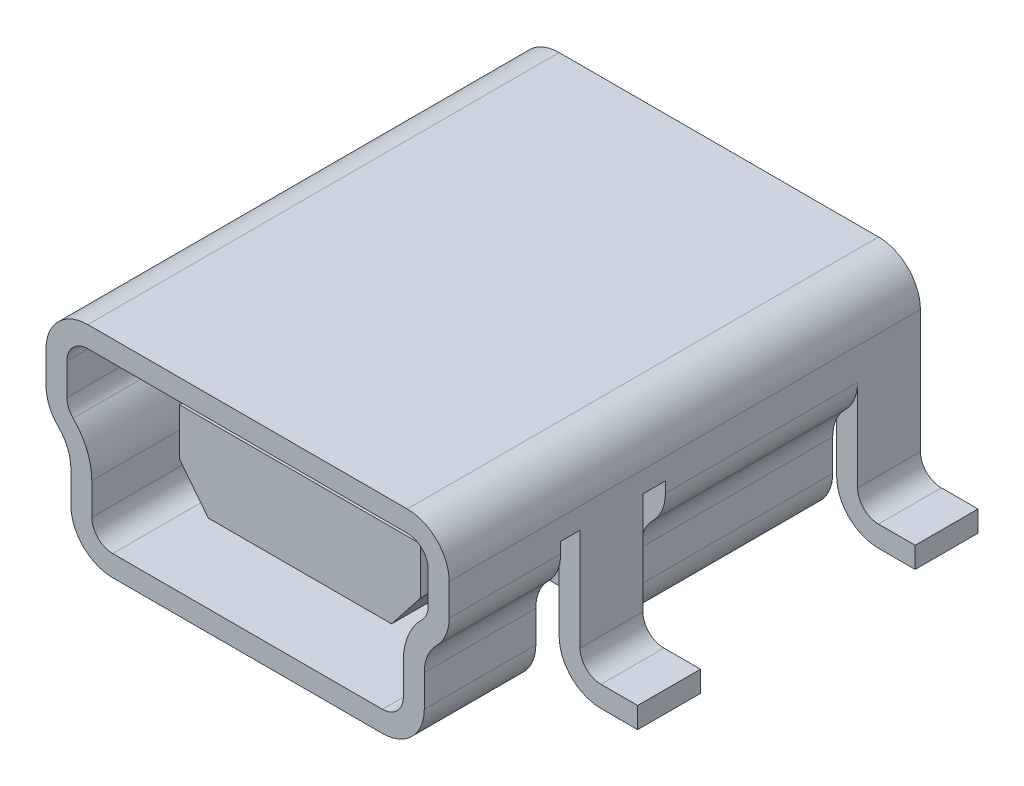
SolidWorks part; units mm, degrees
ref_plane "Front Plane" through (0, 0, 0) normal (0, 0, 1) x (1, 0, 0)
ref_plane "Top Plane" through (0, 0, 0) normal (0, 1, 0) x (1, 0, 0)
ref_plane "Right Plane" through (0, 0, 0) normal (1, 0, 0) x (0, 0, -1)
ref_plane "Plane1" through (0, 0, 3.3) normal (0, 0, 1) x (1, 0, 0)
ref_plane "Plane2" through (0, 0, -2) normal (0, 0, 1) x (1, 0, 0)
sketch "Sketch1" plane through (0, 0, 0) normal (0, 0, 1) x (1, 0, 0)
  line L0 (0, 0) -> (0, 3.95) construction
  line L1 (-2.575, 0) -> (2.575, 0)
  line L2 (-3.85, 2.5439) -> (-3.85, 3.15)
  line L3 (-3.05, 3.95) -> (3.05, 3.95)
  line L4 (-3.6125, 1.975) -> (3.6125, 1.975) construction
  line L5 (-3.375, 1.4061) -> (-3.375, 0.8)
  line L6 (3.375, 1.4061) -> (3.375, 0.8)
  line L7 (3.85, 2.5439) -> (3.85, 3.15)
  arc A0 (-3.375, 1.4061) -> (-3.6125, 1.975) centre (-4.175, 1.4061) ccw
  arc A1 (-3.6125, 1.975) -> (-3.85, 2.5439) centre (-3.05, 2.5439) cw
  arc A2 (-3.85, 3.15) -> (-3.05, 3.95) centre (-3.05, 3.15) cw
  arc A3 (-2.575, 0) -> (-3.375, 0.8) centre (-2.575, 0.8) cw
  arc A4 (2.575, 0) -> (3.375, 0.8) centre (2.575, 0.8) ccw
  arc A5 (3.85, 3.15) -> (3.05, 3.95) centre (3.05, 3.15) ccw
  arc A6 (3.6125, 1.975) -> (3.85, 2.5439) centre (3.05, 2.5439) ccw
  arc A7 (3.375, 1.4061) -> (3.6125, 1.975) centre (4.175, 1.4061) cw
  point P16 (0, 1.975)
  dimension "D1" = 0.8
  dimension "D2" = 6.75
  dimension "D3" = 7.7
  dimension "D4" = 3.95
extrude "Body" add sketch "Sketch1" against normal blind 9 from offset 6.4 thin thin type one direction reverse wall 0.4
sketch "Sketch2" plane through (0, 0, 0) normal (0, -1, 0) x (1, 0, 0)
  line L0 (3.85, -2.6) -> (3.85, 6.4) construction
  line L1 (3.85, 4.27) -> (1.35, 4.27)
  line L2 (3.85, 4.27) -> (3.85, 2.27)
  line L3 (3.85, 2.27) -> (1.35, 2.27)
  line L4 (1.35, 4.27) -> (1.35, 2.27)
  line L5 (-2.575, 6.4) -> (2.575, 6.4) construction
  line L6 (3.85, -2.6) -> (-3.85, -2.6)
  line L7 (3.85, -2.6) -> (3.85, 0.9)
  line L8 (3.85, 0.9) -> (-3.85, 0.9)
  line L9 (-2.575, -2.6) -> (2.575, -2.6) construction
  line L10 (0, 0) -> (0, -3.2675) construction
  line L11 (-3.85, -2.6) -> (-3.85, 0.9)
  line L12 (-1.35, 4.27) -> (-1.35, 2.27)
  line L13 (-3.85, 2.27) -> (-1.35, 2.27)
  line L14 (-3.85, 4.27) -> (-3.85, 2.27)
  line L15 (-3.85, 4.27) -> (-1.35, 4.27)
  point P19 (0, 0.9)
  point P20 (0, -2.6)
  dimension "D1" = 2.13
  dimension "D2" = 2
  dimension "D3" = 1.35
  dimension "D4" = 5.5
extrude "BodyCut" cut sketch "Sketch2" against normal offset from surface (2.75 mm away) 1.2 up to face at (0, 3.95, 1.9)
sketch "Sketch3" plane through (0, 0, -2) normal (0, 0, 1) x (1, 0, 0)
  line L0 (-3.45, 2.75) -> (-3.45, 0.8)
  line L1 (-4.25, 0) -> (-4.95, 0)
  line L2 (0, 0) -> (0, 4.4725) construction
  arc A0 (-4.25, 0) -> (-3.45, 0.8) centre (-4.25, 0.8) ccw
  dimension "D1" = 0.8
  dimension "D2" = 9.9
extrude "Foot1" add sketch "Sketch3" along normal mid plane 1.2 thin thin type one direction wall 0.4
sketch "Sketch4" plane through (0, 0, 3.3) normal (0, 0, 1) x (1, 0, 0)
  line L0 (-4.25, 0) -> (-4.95, 0) construction
  line L1 (-3.45, 2.75) -> (-3.45, 0.8) construction
  line L2 (-4.25, 0) -> (-4.95, 0)
  line L3 (-3.45, 2.75) -> (-3.45, 0.8)
  arc A0 (-4.25, 0) -> (-3.45, 0.8) centre (-4.25, 0.8) ccw construction
  arc A1 (-4.25, 0) -> (-3.45, 0.8) centre (-4.25, 0.8) ccw
extrude "Foot2" add sketch "Sketch4" along normal mid plane 1.2 thin thin type one direction wall 0.4
mirror "Mirror1" about plane through (0, 0, 0) normal (1, 0, 0) of "Foot2", "Foot1"
sketch "Sketch6" plane through (0, 0, 0.9) normal (0, 0, -1) x (-1, 0, 0)
  line L0 (3.45, 3.15) -> (3.45, 0.8) construction
  line L1 (-3.05, 3.55) -> (3.05, 3.55) construction
  line L2 (-3.45, 0.8) -> (-3.45, 3.15) construction
  line L3 (3.45, 3.15) -> (3.45, 2.75)
  line L4 (-3.05, 3.55) -> (3.05, 3.55)
  line L5 (-3.45, 2.75) -> (-3.45, 3.15)
  line L12 (-3.375, 1.4061) -> (-3.375, 0.8)
  line L13 (-2.575, 0) -> (2.575, 0)
  line L14 (3.375, 0.8) -> (3.375, 1.4061)
  line L15 (3.85, 2.5439) -> (3.85, 2.75)
  line L16 (3.85, 2.75) -> (3.45, 2.75)
  line L17 (3.45, 2.75) -> (3.45, 2.5439)
  line L18 (2.975, 1.4061) -> (2.975, 0.8)
  line L19 (2.575, 0.4) -> (-2.575, 0.4)
  line L20 (-2.975, 0.8) -> (-2.975, 1.4061)
  line L21 (-3.45, 2.5439) -> (-3.45, 2.75)
  line L22 (-3.45, 2.75) -> (-3.85, 2.75)
  line L23 (-3.85, 2.75) -> (-3.85, 2.5439)
  line L24 (-3.375, 1.4061) -> (-3.375, 0.8)
  line L25 (-2.575, 0) -> (2.575, 0)
  line L26 (3.375, 0.8) -> (3.375, 1.4061)
  line L27 (3.85, 2.5439) -> (3.85, 2.75)
  line L28 (3.85, 2.75) -> (3.45, 2.75)
  line L34 (-3.45, 2.75) -> (-3.85, 2.75)
  line L35 (-3.85, 2.75) -> (-3.85, 2.5439)
  arc A0 (3.45, 3.15) -> (3.05, 3.55) centre (3.05, 3.15) ccw construction
  arc A1 (-3.05, 3.55) -> (-3.45, 3.15) centre (-3.05, 3.15) ccw construction
  arc A2 (3.45, 3.15) -> (3.05, 3.55) centre (3.05, 3.15) ccw
  arc A3 (-3.05, 3.55) -> (-3.45, 3.15) centre (-3.05, 3.15) ccw
  arc A12 (-3.85, 2.5439) -> (-3.6125, 1.975) centre (-3.05, 2.5439) ccw
  arc A13 (-3.375, 1.4061) -> (-3.6125, 1.975) centre (-4.175, 1.4061) ccw
  arc A14 (-3.375, 0.8) -> (-2.575, 0) centre (-2.575, 0.8) ccw
  arc A15 (2.575, 0) -> (3.375, 0.8) centre (2.575, 0.8) ccw
  arc A16 (3.6125, 1.975) -> (3.375, 1.4061) centre (4.175, 1.4061) ccw
  arc A17 (3.6125, 1.975) -> (3.85, 2.5439) centre (3.05, 2.5439) ccw
  arc A18 (3.3312, 2.2594) -> (3.45, 2.5439) centre (3.05, 2.5439) ccw
  arc A19 (3.3312, 2.2594) -> (2.975, 1.4061) centre (4.175, 1.4061) ccw
  arc A20 (2.575, 0.4) -> (2.975, 0.8) centre (2.575, 0.8) ccw
  arc A21 (-2.975, 0.8) -> (-2.575, 0.4) centre (-2.575, 0.8) ccw
  arc A22 (-2.975, 1.4061) -> (-3.3313, 2.2594) centre (-4.175, 1.4061) ccw
  arc A23 (-3.45, 2.5439) -> (-3.3313, 2.2594) centre (-3.05, 2.5439) ccw
  arc A24 (-3.85, 2.5439) -> (-3.6125, 1.975) centre (-3.05, 2.5439) ccw
  arc A25 (-3.375, 1.4061) -> (-3.6125, 1.975) centre (-4.175, 1.4061) ccw
  arc A26 (-3.375, 0.8) -> (-2.575, 0) centre (-2.575, 0.8) ccw
  arc A27 (2.575, 0) -> (3.375, 0.8) centre (2.575, 0.8) ccw
  arc A28 (3.6125, 1.975) -> (3.375, 1.4061) centre (4.175, 1.4061) ccw
  arc A29 (3.6125, 1.975) -> (3.85, 2.5439) centre (3.05, 2.5439) ccw
  dimension "D1" = 0
extrude "Core1" add sketch "Sketch6" along normal up to surface (2.3 mm away) up to face at (4.0939, 0.9564, -1.4)
sketch "Sketch7" plane through (0, 0, 0.9) normal (0, 0, 1) x (1, 0, 0)
  line L0 (0, 0) -> (0, 3.95) construction
  line L1 (-2.3, 2.5) -> (2.3, 2.5)
  line L2 (-2.3, 2.5) -> (-2.3, 1.6)
  line L3 (-1.75, 0.9) -> (1.75, 0.9)
  line L4 (2.3, 1.6) -> (1.75, 0.9)
  line L5 (-2.575, 0) -> (2.575, 0) construction
  line L7 (3.05, 3.95) -> (-3.05, 3.95) construction
  line L8 (-2.3, 1.6) -> (-1.75, 0.9)
  line L9 (2.3, 2.5) -> (2.3, 1.6)
  line L10 (-2.575, 0.4) -> (2.575, 0.4) construction
  point P13 (0, 0.9)
  point P14 (0, 2.5)
  dimension "D1" = 3.5
  dimension "D2" = 1.6
  dimension "D3" = 0.5
  dimension "D4" = 4.6
  dimension "D5" = 0.7
extrude "Core2" add sketch "Sketch7" along normal offset from surface (4.5 mm away) 1 up to face at (0, 2.019, 6.4)
sketch "Sketch8" plane through (0, 0, 6.4) normal (0, 0, 1) x (1, 0, 0)
  line L0 (0, 0) -> (0, 4.9487) construction
  line L1 (3.05, 3.95) -> (-3.05, 3.95) construction
  line L2 (1.15, 3.95) -> (-1.15, 3.95)
  line L3 (1.15, 3.95) -> (1.15, 4.6)
  line L4 (1.15, 4.6) -> (-1.15, 4.6)
  line L5 (-1.95, 3.95) -> (-1.95, 4.3)
  line L6 (-2.95, 4.3) -> (-1.95, 4.3)
  line L7 (2.95, 3.95) -> (1.95, 3.95)
  line L8 (2.95, 3.95) -> (2.95, 4.3)
  line L9 (2.95, 4.3) -> (1.95, 4.3)
  line L10 (1.95, 3.95) -> (1.95, 4.3)
  line L11 (-2.95, 3.95) -> (-2.95, 4.3)
  line L12 (-2.95, 3.95) -> (-1.95, 3.95)
  line L13 (-1.15, 3.95) -> (-1.15, 4.6)
  point P18 (0, 4.6)
  point P19 (0, 3.95)
  dimension "D1" = 2.3
  dimension "D2" = 0.65
  dimension "D3" = 0.35
  dimension "D4" = 1
  dimension "D5" = 4.9
extrude "TopKEEPOUT" [suppressed] add sketch "Sketch8" against normal blind 4.5 from offset 1.1 offset against normal yes
sketch "Sketch9" plane through (0, 0, 0) normal (0, -1, 0) x (1, 0, 0)
  line L0 (0, 0) -> (0, -1.8039) construction
  circle A0 centre (-1.75, 0) radius 0.4
  circle A1 centre (1.75, 0) radius 0.4
  dimension "D1" = 0.8
  dimension "D2" = 3.5
extrude "LocatePins" add sketch "Sketch9" along normal blind 0.5
